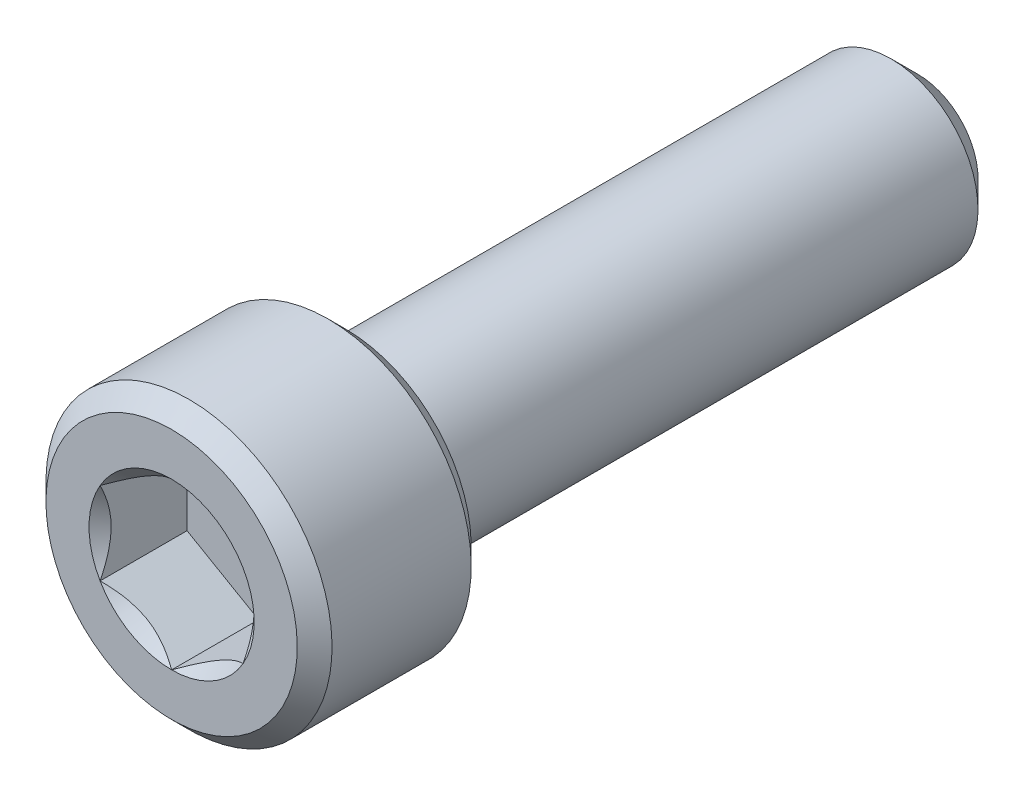
SolidWorks part; units mm, degrees
material "Alloy Steel"
ref_plane "Front Plane" through (0, 0, 0) normal (0, 0, 1) x (1, 0, 0)
ref_plane "Top Plane" through (0, 0, 0) normal (0, 1, 0) x (1, 0, 0)
ref_plane "Right Plane" through (0, 0, 0) normal (1, 0, 0) x (0, 0, -1)
sketch "Sketch1" plane through (0, 0, 0) normal (1, 0, 0) x (0, 0, -1)
  line L0 (10.3505, 0) -> (-10.3505, 0) construction
  line L1 (-10.3505, 0) -> (-10.3505, 3.4861)
  line L2 (-10.3505, 3.4861) -> (-9.8679, 3.9687)
  line L3 (-9.8679, 3.9687) -> (-6.0071, 3.9687)
  line L4 (-6.0071, 3.9687) -> (-5.5245, 3.4861)
  line L5 (-5.5245, 3.4861) -> (-5.5245, 2.413)
  line L6 (-5.5245, 2.413) -> (9.6097, 2.413)
  line L7 (9.6097, 2.413) -> (10.3505, 1.6722)
  line L8 (10.3505, 1.6722) -> (10.3505, 0)
  line L9 (10.2844, 2.5276) -> (11.3427, 2.5276) construction
  line L10 (11.3427, 2.5276) -> (10.8135, 1.611) construction
  line L11 (10.8135, 1.611) -> (10.2844, 2.5276) construction
  line L12 (10.3505, 2.413) -> (11.2765, 2.413) construction
  line L13 (10.8135, 2.5276) -> (10.8135, 2.413) construction
  line L14 (10.7474, 1.7256) -> (10.8797, 1.7256) construction
  line L15 (10.8135, 1.7256) -> (10.8135, 1.611) construction
  line L16 (10.3174, 2.4703) -> (11.3096, 2.4703)
  line L17 (11.3096, 2.4703) -> (10.8797, 1.7256)
  line L18 (10.8797, 1.7256) -> (10.7474, 1.7256)
  line L19 (10.7474, 1.7256) -> (10.3174, 2.4703)
  line L20 (9.6097, -2.413) -> (7.7047, -2.413) construction
  point P3 (-9.6266, 3.9687)
  point P4 (0, 0)
  point P25 (10.8135, 2.4703)
  point P26 (10.3505, 2.413)
  point P28 (-6.2484, 3.9687)
  point P29 (-7.9375, 3.9687)
  point P33 (7.7047, -2.413)
  dimension "Head Ht" = 4.826
  dimension "Screw Size" = 4.826
  dimension "Head Dia" = 7.9375
  dimension "D1" = 45
  dimension "D2" = 45
  dimension "D3" = 0.4826
  dimension "D4" = 0.4826
  dimension "Pitch" = 1.0583
  dimension "D5" = 0.1323
  dimension "D6" = 0.7408
  dimension "D7" = 1.905
  dimension "Length" = 15.875
  dimension "D8" = 0.2413
  dimension "D9" = 0.2413
sketch "Sketch2" plane through (0, 0, 0) normal (0, 0, 1) x (1, 0, 0)
  line L1 (0, 2.2914) -> (-1.9844, 1.1457)
  line L2 (-1.9844, 1.1457) -> (-1.9844, -1.1457)
  line L3 (-1.9844, -1.1457) -> (0, -2.2914)
  line L4 (0, -2.2914) -> (1.9844, -1.1457)
  line L5 (1.9844, -1.1457) -> (1.9844, 1.1457)
  line L6 (1.9844, 1.1457) -> (0, 2.2914)
  line L8 (0, -3.9687) -> (0, 3.9687) construction
  circle A0 centre (0, 0) radius 1.9844 construction
  circle A1 centre (0, 0) radius 3.9687
  circle A2 centre (0, 0) radius 18.0975 construction
  point P1 (0, 3.9687)
  point P19 (0, 0)
  dimension "D1" = 7.9375
  dimension "D3" = 36.195
  dimension "Drive Size" = 3.9688
sketch "Sketch3" plane through (0, 0, 0) normal (1, 0, 0) x (0, 0, -1)
  line L0 (10.3505, 0) -> (-10.3505, 0) construction
  line L1 (-10.3505, 0) -> (-10.3505, 3.4861) construction
  line L2 (-10.3505, 3.4861) -> (-9.8679, 3.9687) construction
  line L3 (-9.8679, 3.9687) -> (-6.0071, 3.9687) construction
  line L4 (-6.0071, 3.9687) -> (-5.5245, 3.4861) construction
  line L5 (-5.5245, 3.4861) -> (-5.5245, 2.413) construction
  line L6 (-5.5245, 2.413) -> (9.6097, 2.413) construction
  line L7 (9.6097, 2.413) -> (10.3505, 1.6722) construction
  line L8 (10.3505, 1.6722) -> (10.3505, 0) construction
  line L9 (10.3505, 0) -> (-10.3505, 0)
  line L10 (-10.3505, 0) -> (-10.3505, 3.4861)
  line L11 (-10.3505, 3.4861) -> (-9.8679, 3.9687)
  line L12 (-9.8679, 3.9687) -> (-6.0071, 3.9687)
  line L13 (-6.0071, 3.9687) -> (-5.5245, 3.4861)
  line L14 (-5.5245, 3.4861) -> (-5.5245, 2.413)
  line L15 (-5.5245, 2.413) -> (9.6097, 2.413)
  line L16 (9.6097, 2.413) -> (10.3505, 1.6722)
  line L17 (10.3505, 1.6722) -> (10.3505, 0)
revolve "Revolve1" add sketch "Sketch3" angle 360 about L0
sketch "Sketch4" plane through (0, 0, 10.3505) normal (0, 0, 1) x (1, 0, 0)
  line L0 (0, -2.2914) -> (1.9844, -1.1457) construction
  line L1 (1.9844, -1.1457) -> (1.9844, 1.1457) construction
  line L2 (1.9844, 1.1457) -> (0, 2.2914) construction
  line L3 (0, 2.2914) -> (-1.9844, 1.1457) construction
  line L4 (-1.9844, 1.1457) -> (-1.9844, -1.1457) construction
  line L5 (-1.9844, -1.1457) -> (0, -2.2914) construction
  line L6 (0, -2.2914) -> (1.9844, -1.1457)
  line L7 (1.9844, -1.1457) -> (1.9844, 1.1457)
  line L8 (1.9844, 1.1457) -> (0, 2.2914)
  line L9 (0, 2.2914) -> (-1.9844, 1.1457)
  line L10 (-1.9844, 1.1457) -> (-1.9844, -1.1457)
  line L11 (-1.9844, -1.1457) -> (0, -2.2914)
extrude "Cut-Extrude1" cut sketch "Sketch4" against normal blind 2.413
sketch "Sketch5" plane through (0, 0, 10.3505) normal (0, 0, 1) x (1, 0, 0)
  circle A0 centre (0, 0) radius 2.2914
extrude "Cut-Extrude3" cut sketch "Sketch5" against normal through all draft 45
ref_axis "Center Axis1" through (0, 0, 5.5245) along (0, 0, -1)
split "Split1" [suppressed] bodies to split 107
sketch "Sketch6" [suppressed] plane through (0, 0, -10.3505) normal (0, 0, -1) x (-1, 0, 0)
  circle A0 centre (0, 0) radius 2.413 construction
  circle A1 centre (0, 0) radius 2.413
curve "Helix/Spiral1" [suppressed] pitch 1.0583 height 16.9333 turns 16
sketch "Sketch7" [suppressed] plane through (0, 0, 0) normal (1, 0, 0) x (0, 0, -1)
  line L0 (10.3174, 2.4703) -> (11.3096, 2.4703) construction
  line L1 (11.3096, 2.4703) -> (10.8797, 1.7256) construction
  line L2 (10.8797, 1.7256) -> (10.7474, 1.7256) construction
  line L3 (10.7474, 1.7256) -> (10.3174, 2.4703) construction
  line L4 (10.3174, 2.4703) -> (11.3096, 2.4703)
  line L5 (11.3096, 2.4703) -> (10.8797, 1.7256)
  line L6 (10.8797, 1.7256) -> (10.7474, 1.7256)
  line L7 (10.7474, 1.7256) -> (10.3174, 2.4703)
sweep "Cut-Sweep1" [suppressed] cut profiles "Sketch7" path "Helix/Spiral1"
sketch "Sketch8" [suppressed] plane through (0, 0, 5.5245) normal (0, 0, -1) x (-1, 0, 0)
  circle A0 centre (0, 0) radius 2.413
  point P3 (0, 2.413)
extrude "Boss-Extrude1" [suppressed] add sketch "Sketch8" along normal blind 2.54 draft 80
equation "\"D3@Sketch1\"=\"Head Ht@Sketch1\"/10"
equation "\"D4@Sketch1\"=\"Head Ht@Sketch1\"/10"
equation "\"D5@Sketch1\"=\"Pitch@Sketch1\"/8"
equation "\"D6@Sketch1\"=\"Pitch@Sketch1\"*.7"
equation "\"D7@Sketch1\"=\"Pitch@Sketch1\"*2.5-\"D6@Sketch1\""
equation "\"D1@Cut-Extrude1\"=\"Head Ht@Sketch1\"/2"
equation "\"D4@Helix/Spiral1\"=\"Pitch@Sketch1\""
equation "\"D3@Helix/Spiral1\"=\"Length@Sketch1\"+\"D4@Helix/Spiral1\""
equation "\"D8@Sketch1\"=\"D4@Sketch1\"/2"
equation "\"D9@Sketch1\"=\"D3@Sketch1\"/2"
